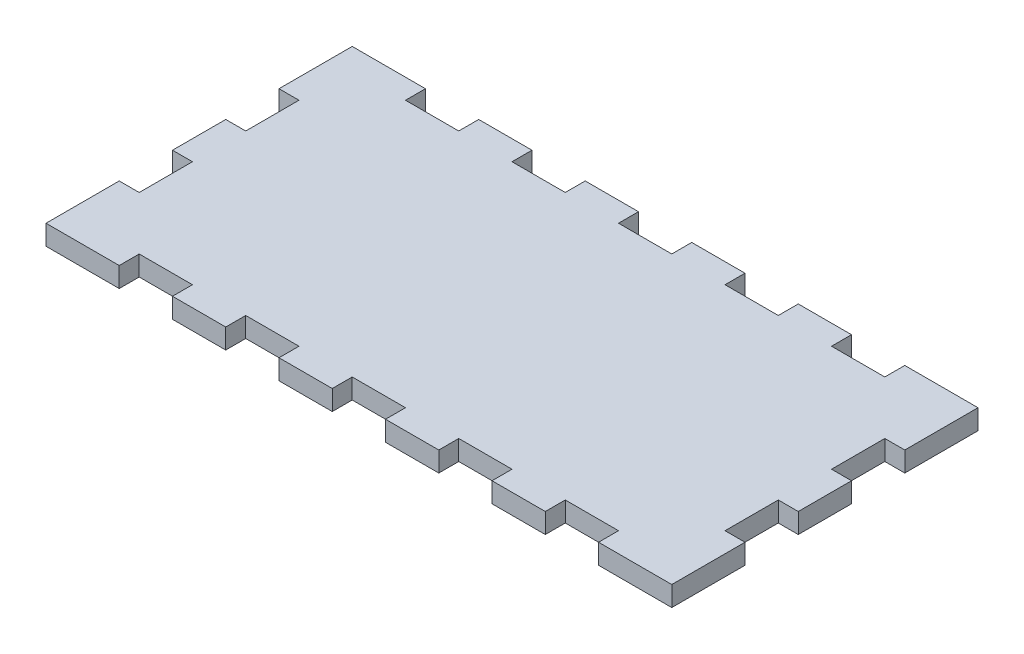
SolidWorks part; units mm, degrees
ref_plane "Front Plane" through (0, 0, 0) normal (0, 0, 1) x (1, 0, 0)
ref_plane "Top Plane" through (0, 0, 0) normal (0, 1, 0) x (1, 0, 0)
ref_plane "Right Plane" through (0, 0, 0) normal (1, 0, 0) x (0, 0, -1)
sketch "Sketch2" plane through (0, 0, 0) normal (0, 1, 0) x (1, 0, 0)
  line L1 (139.7, -63.5) -> (-139.7, -63.5)
  line L2 (139.7, -63.5) -> (139.7, 63.5)
  line L3 (139.7, 63.5) -> (-139.7, 63.5)
  line L4 (-139.7, -63.5) -> (-139.7, 63.5)
  line L5 (139.7, -63.5) -> (-139.7, 63.5) construction
  line L6 (139.7, 63.5) -> (-139.7, -63.5) construction
  point P0 (0, 0)
  dimension "D1" = 279.4
  dimension "D2" = 127
extrude "Boss-Extrude1" add sketch "Sketch2" along normal blind 9.525
sketch "Sketch3" plane through (0, 0, 63.5) normal (0, 0, 1) x (1, 0, 0)
  line L0 (-139.7, 9.525) -> (139.7, 9.525) construction
  line L1 (-139.7, 0) -> (-114.3, 0)
  line L2 (-139.7, 0) -> (-139.7, 9.525)
  line L3 (-139.7, 9.525) -> (-114.3, 9.525)
  line L4 (-114.3, 0) -> (-114.3, 9.525)
  dimension "D1" = 25.4
extrude "Boss-Extrude2" add sketch "Sketch3" along normal blind 9.525
pattern_linear "LPattern1" count 6 spacing 50.8 along (1, 0, 0) of "Boss-Extrude2"
mirror "Mirror1" about plane through (0, 0, 0) normal (0, 0, 1) of "LPattern1"
sketch "Sketch4" plane through (139.7, 0, 0) normal (1, 0, 0) x (0, 0, -1)
  line L0 (-73.025, 0) -> (73.025, 0) construction
  line L1 (-63.5, 0) -> (-38.1, 0)
  line L2 (-63.5, 0) -> (-63.5, 9.525)
  line L3 (-63.5, 9.525) -> (-38.1, 9.525)
  line L4 (-38.1, 0) -> (-38.1, 9.525)
  line L5 (-73.025, 9.525) -> (73.025, 9.525) construction
  line L6 (-73.025, 0) -> (-73.025, 9.525) construction
  dimension "D1" = 9.525
  dimension "D2" = 25.4
extrude "Boss-Extrude3" add sketch "Sketch4" along normal blind 9.525
pattern_linear "LPattern2" count 3 spacing 50.8 along (0, 0, -1) of "Boss-Extrude3"
mirror "Mirror2" about plane through (0, 0, 0) normal (1, 0, 0) of "LPattern2"
sketch "Sketch6" plane through (0, 0, 63.5) normal (0, 0, 1) x (1, 0, 0)
  line L1 (149.225, 9.525) -> (139.7, 9.525)
  line L2 (149.225, 9.525) -> (149.225, 0)
  line L3 (149.225, 0) -> (139.7, 0)
  line L4 (139.7, 9.525) -> (139.7, 0)
extrude "Boss-Extrude4" add sketch "Sketch6" along normal blind 9.525
mirror "Mirror3" about plane through (0, 0, 0) normal (1, 0, 0) of "Boss-Extrude4"
mirror "Mirror4" about plane through (0, 0, 0) normal (0, 0, 1) of "Mirror3"
sketch "Sketch7" plane through (0, 9.525, 0) normal (0, 1, 0) x (1, 0, 0)
  circle A0 centre (-29.2864, 23.8119) radius 0.032
  circle A1 centre (-23.072, 14.7922) radius 0.1056
  circle A2 centre (27.5, 22.9863) radius 2
  circle A3 centre (22.5, 12.9863) radius 2
extrude "Cut-Extrude1" [suppressed] cut sketch "Sketch7" against normal through all
sketch "Sketch8" plane through (0, 9.525, 0) normal (0, 1, 0) x (1, 0, 0)
  circle A0 centre (-25.974, 23.4033) radius 0.0509
  circle A1 centre (-24.0521, 14.3728) radius 0.0812
  circle A2 centre (-27.5, -10.3679) radius 2
  circle A3 centre (-22.5, -20.3679) radius 2
extrude "Cut-Extrude3" [suppressed] cut sketch "Sketch8" against normal through all contours A2 A0 | A3
sketch "Sketch9" [suppressed] plane through (0, 0, 0) normal (0, -1, 0) x (1, 0, 0)
  circle A0 centre (-22.5, -12.9863) radius 3.81
  circle A1 centre (-27.5, -22.9863) radius 3.81
  circle A2 centre (22.5, -12.9863) radius 3.81
  circle A3 centre (27.5, -22.9863) radius 3.81
  dimension "D1" = 7.62
  dimension "D2" = 7.62
  dimension "D3" = 7.62
  dimension "D4" = 7.62
extrude "Cut-Extrude4" [suppressed] cut sketch "Sketch9" against normal blind 4.7625
